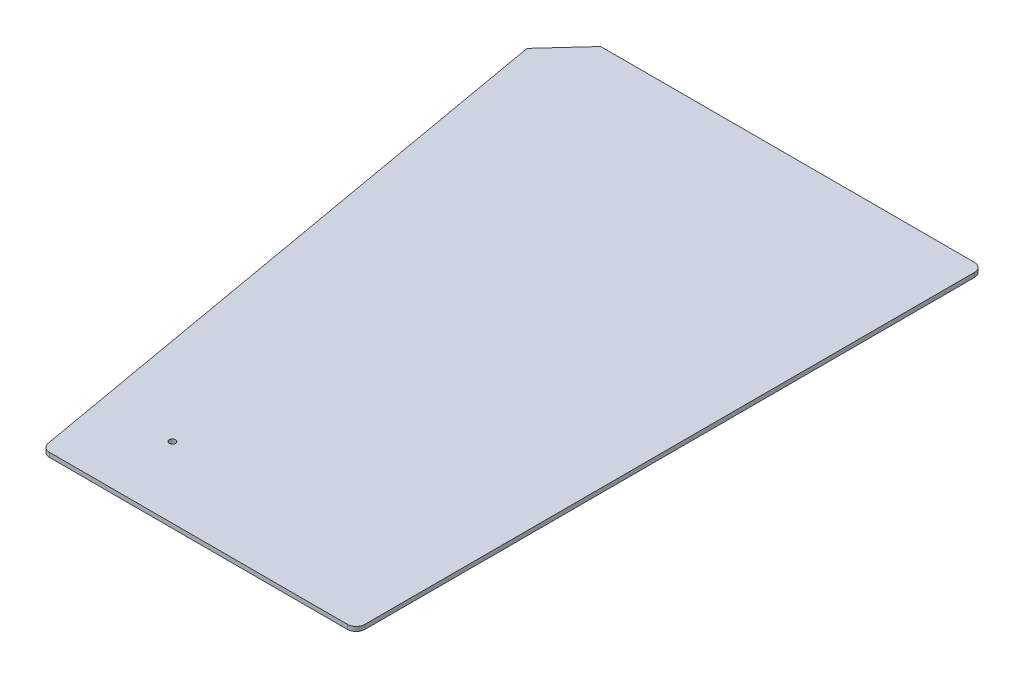
SolidWorks part; units mm, degrees
material "ABS PC"
ref_plane "Front Plane" through (0, 0, 0) normal (0, 0, 1) x (1, 0, 0)
ref_plane "Top Plane" through (0, 0, 0) normal (0, 1, 0) x (1, 0, 0)
ref_plane "Right Plane" through (0, 0, 0) normal (1, 0, 0) x (0, 0, -1)
sketch "Sketch1" plane through (0, 0, 0) normal (0, 1, 0) x (1, 0, 0)
  line L0 (-175.22, 258.837) -> (-145.0753, 258.837) construction
  line L1 (-90.4997, -191.4171) -> (123.23, -191.4171)
  line L2 (-96.7533, -186.1698) -> (-170.3554, 231.2486)
  line L3 (-145.0753, 258.837) -> (123.23, 258.837)
  line L4 (129.58, -185.0671) -> (129.58, 252.487)
  line L5 (-95.828, -191.4171) -> (129.58, 258.837) construction
  line L6 (-175.22, 258.837) -> (129.58, -191.4171) construction
  line L7 (-170.3554, 231.2486) -> (-175.22, 258.837) construction
  line L8 (-145.0753, 258.837) -> (-170.3554, 231.2486)
  arc A1 (129.58, -185.0671) -> (123.23, -191.4171) centre (123.23, -185.0671) cw
  arc A2 (129.58, 252.487) -> (123.23, 258.837) centre (123.23, 252.487) ccw
  arc A4 (-90.4997, -191.4171) -> (-96.7533, -186.1698) centre (-90.4997, -185.0671) cw
  point P0 (0, 0)
  dimension "D3" = 22.225
  dimension "D5" = 6.35
  dimension "D1" = 457.2
  dimension "D2" = 304.8
  dimension "D4" = 80
  dimension "D6" = 127.5
extrude "Stock to Size" add sketch "Sketch1" along normal blind 3.175
sketch "Sketch3" [suppressed] plane through (0, 0, 0) normal (0, 0, 1) x (1, 0, 0)
  line L1 (-133.0134, -355.6) -> (133.6866, -355.6)
  line L2 (-139.3634, -349.25) -> (-139.3634, 349.25)
  line L3 (-133.0134, 355.6) -> (133.6866, 355.6)
  line L4 (140.0366, -349.25) -> (140.0366, 349.25)
  line L5 (-139.3634, -355.6) -> (140.0366, 355.6) construction
  line L6 (-139.3634, 355.6) -> (140.0366, -355.6) construction
  arc A1 (140.0366, -349.25) -> (133.6866, -355.6) centre (133.6866, -349.25) cw
  arc A2 (140.0366, 349.25) -> (133.6866, 355.6) centre (133.6866, 349.25) ccw
  arc A4 (-133.0134, -355.6) -> (-139.3634, -349.25) centre (-133.0134, -349.25) cw
  arc A5 (-139.3634, 349.25) -> (-133.0134, 355.6) centre (-133.0134, 349.25) cw
  point P0 (0.3366, 0)
  dimension "D5" = 6.35
  dimension "D1" = 711.2
  dimension "D2" = 279.4
  dimension "D4" = 90
extrude "Front Stock" [suppressed] add sketch "Sketch3" along normal blind 3.175
sketch "Sketch2" plane through (0, 3.175, 0) normal (0, 1, 0) x (1, 0, 0)
  line L2 (-170.3554, 231.2486) -> (-96.7533, -186.1698) construction
  line L3 (-90.4997, -191.4171) -> (123.23, -191.4171) construction
  circle A0 centre (-53.2018, -140.6171) radius 2.286
  dimension "D1" = 4.572
  dimension "D2" = 50.8
  dimension "D3" = 50.8
extrude "Mounting Hole" cut sketch "Sketch2" against normal through all
